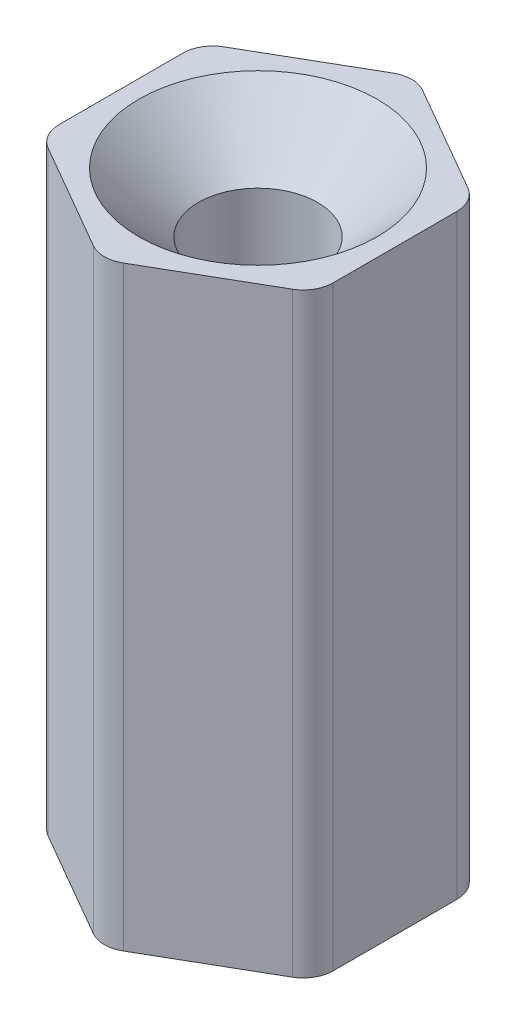
SolidWorks part; units mm, degrees
material "Free-Cutting Brass, UNS C36000"
ref_plane "Front" through (0, 0, 0) normal (0, 0, 1) x (1, 0, 0)
ref_plane "Top" through (0, 0, 0) normal (0, 1, 0) x (1, 0, 0)
ref_plane "Right" through (0, 0, 0) normal (1, 0, 0) x (0, 0, -1)
sketch "Sketch1" plane through (0, 0, 0) normal (0, 1, 0) x (1, 0, 0)
  line L1 (0, 2.6558) -> (-2.3, 1.3279)
  line L2 (-2.3, 1.3279) -> (-2.3, -1.3279)
  line L3 (-2.3, -1.3279) -> (0, -2.6558)
  line L4 (0, -2.6558) -> (2.3, -1.3279)
  line L5 (2.3, -1.3279) -> (2.3, 1.3279)
  line L6 (2.3, 1.3279) -> (0, 2.6558)
  circle A0 centre (0, 0) radius 2.3 construction
  point P1 (0, 0)
  dimension "D1" = 4.6
extrude "Boss-Extrude1" add sketch "Sketch1" along normal blind 10
sketch "Sketch2" plane through (0, 10, 0) normal (0, 1, 0) x (1, 0, 0)
  circle A0 centre (0, 0) radius 1
  dimension "D1" = 2
extrude "Cut-Extrude1" cut sketch "Sketch2" against normal through all
chamfer "Chamfer2" distance 1 angle 45 2 edges at (0, 0, 1) (0, 10, 1)
fillet "Fillet1" radius 0.5 6 edges at (0, 5, 2.6558) (-2.3, 5, 1.3279) (-2.3, 5, -1.3279) (0, 5, -2.6558) (2.3, 5, -1.3279) (2.3, 5, 1.3279)
